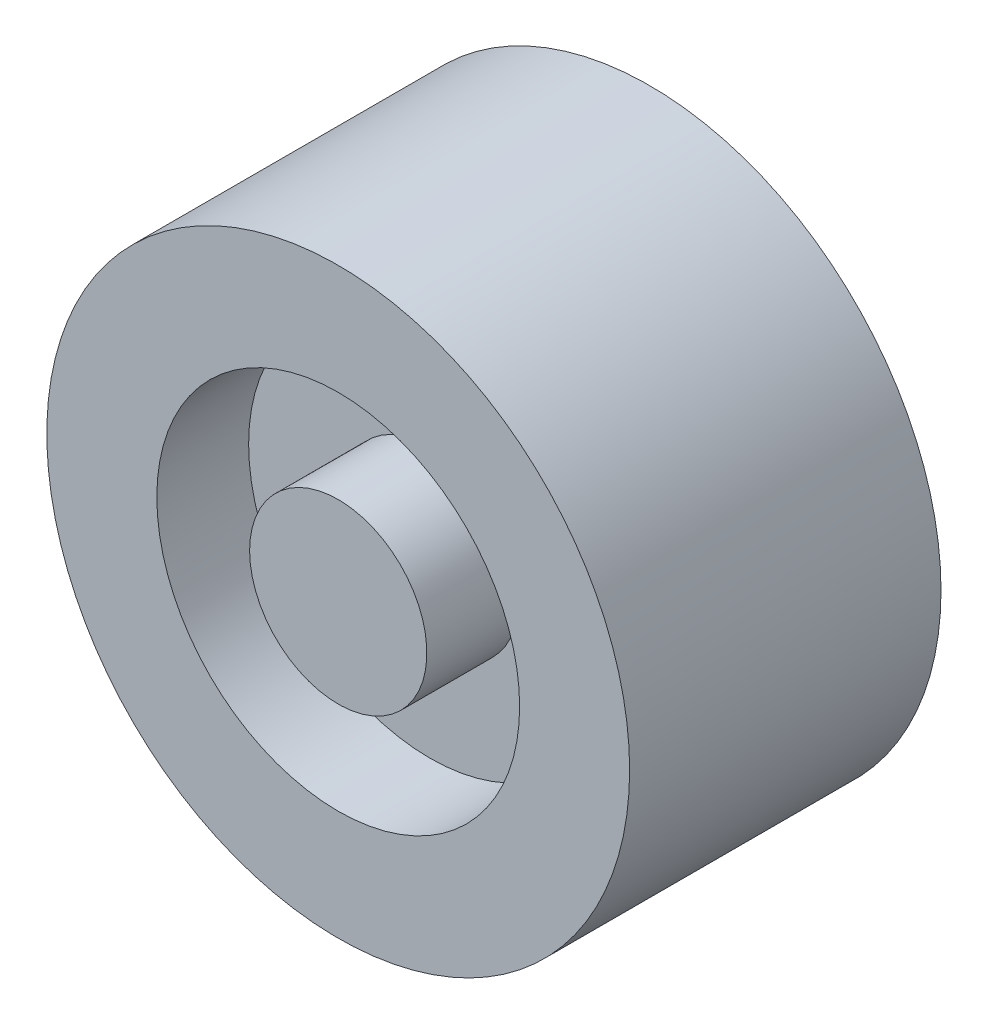
SolidWorks part; units mm, degrees
ref_plane "Front Plane" through (0, 0, 0) normal (0, 0, 1) x (1, 0, 0)
ref_plane "Top Plane" through (0, 0, 0) normal (0, 1, 0) x (1, 0, 0)
ref_plane "Right Plane" through (0, 0, 0) normal (1, 0, 0) x (0, 0, -1)
sketch "Sketch1" plane through (0, 0, 0) normal (0, 0, 1) x (1, 0, 0)
  circle A0 centre (0, 0) radius 15.0762
  dimension "D1" = 30.1523
extrude "Boss-Extrude1" add sketch "Sketch1" along normal blind 16.1087
sketch "Sketch2" plane through (0, 0, 0) normal (0, 0, -1) x (-1, 0, 0)
  circle A0 centre (0, 0) radius 9.3853
  circle A1 centre (0, 0) radius 4.5847
  dimension "D1" = 18.7706
  dimension "D2" = 9.1694
extrude "Cut-Extrude1" cut sketch "Sketch2" against normal blind 4.7498
ref_plane "Plane1" through (0, 0, 8.0543) normal (0, 0, -1) x (-1, 0, 0)
mirror "Mirror1" about plane through (0, 0, 8.0543) normal (0, 0, -1) of "Cut-Extrude1"
